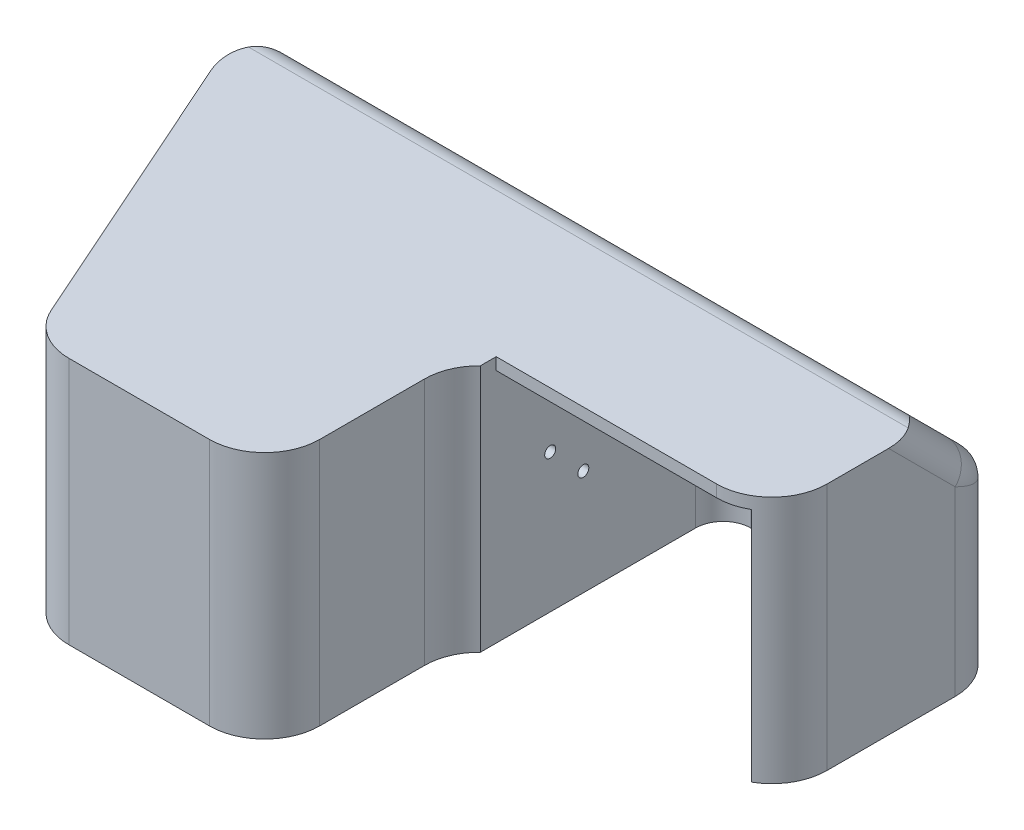
SolidWorks part; units mm, degrees
ref_plane "前视基准面" through (0, 0, 0) normal (0, 0, 1) x (1, 0, 0)
ref_plane "上视基准面" through (0, 0, 0) normal (0, 1, 0) x (1, 0, 0)
ref_plane "右视基准面" through (0, 0, 0) normal (1, 0, 0) x (0, 0, -1)
other "Configuration Table"
sketch "草图2" plane through (0, 0, 0) normal (0, 1, 0) x (1, 0, 0)
  line L0 (-10, 0) -> (-35.5013, 0)
  line L1 (53, 49) -> (53, 63)
  line L3 (0, 10) -> (0, 29)
  line L4 (10, 39) -> (43, 39)
  line L5 (-70, 63) -> (-44.6394, 5.9386)
  line L6 (-42, 0) -> (-75.4277, 75.2123)
  line L7 (-70.8587, 82.243) -> (43, 82.243)
  line L8 (53, 72.243) -> (53, 63)
  arc A0 (0, 29) -> (10, 39) centre (10, 29) cw
  arc A1 (53, 72.243) -> (43, 82.243) centre (43, 72.243) ccw
  arc A2 (53, 49) -> (43, 39) centre (43, 49) cw
  arc A3 (0, 10) -> (-10, 0) centre (-10, 10) cw
  arc A4 (-35.5013, 0) -> (-44.6394, 5.9386) centre (-35.5013, 10) cw
  arc A5 (-70.8587, 82.243) -> (-75.4277, 75.2123) centre (-70.8587, 77.243) ccw
  point P11 (0, 39)
  point P16 (53, 39)
  point P19 (0, 0)
  dimension "D3" = 10
  dimension "D6" = 5
  dimension "D1" = 42
  dimension "D2" = 123
  dimension "D4" = 39
  dimension "D5" = 53
extrude "凸台-拉伸3" add sketch "草图2" along normal blind 45 contours L7 A5 L6 L5 A4 L0 A3 L3 A0 L4 A2 L1 L8 A1 region at (-13.0814, 0, -50.1616)
sketch "草图3" plane through (53, 0, 0) normal (1, 0, 0) x (0, 0, -1)
  line L0 (82.243, 45) -> (67.243, 45)
  line L1 (49, 45) -> (72.243, 45) construction
  line L2 (82.243, 45) -> (82.243, 30)
  line L3 (67.243, 45) -> (82.243, 30)
  dimension "D1" = 15
  dimension "D2" = 15
extrude "切除-拉伸1" cut sketch "草图3" against normal blind 4005
fillet "圆角1" radius 5 6 edges at (-73.6568, 41.0153, -71.2277) (-75.0511, 32.2754, -79.9676) (53, 42.5, -69.743) (50.0711, 32.9289, -79.3141) (-13.9293, 30, -82.243) (-9.4429, 45, -67.243)
sketch "草图4" plane through (0, 0, 0) normal (0, -1, 0) x (1, 0, 0)
  line L1 (3, -39) -> (48, -39)
  line L2 (3, -39) -> (3, -74)
  line L3 (8, -79) -> (43, -79)
  line L4 (48, -39) -> (48, -74)
  line L5 (10, -39) -> (43, -39) construction
  line L6 (53, -49) -> (53, -72.243) construction
  arc A0 (48, -74) -> (43, -79) centre (43, -74) cw
  arc A1 (8, -79) -> (3, -74) centre (8, -74) cw
  point P10 (48, -79)
  dimension "D5" = 5
  dimension "D1" = 45
  dimension "D2" = 40
  dimension "D3" = 0
  dimension "D4" = 5
extrude "切除-拉伸3" cut sketch "草图4" against normal blind 25
sketch "草图5" plane through (0, 0, 0) normal (0, -1, 0) x (1, 0, 0)
  line L1 (3, -39) -> (48.6547, -39)
  line L2 (3, -39) -> (3, 1.5945)
  line L3 (3, 1.5945) -> (48.6547, 1.5945)
  line L4 (48.6547, -39) -> (48.6547, 1.5945)
extrude "切除-拉伸4" cut sketch "草图5" against normal blind 25 contours L2 L3 L4 L1
sketch "草图6" plane through (0, 0, -39) normal (0, 0, 1) x (1, 0, 0)
  line L0 (3, 25) -> (3, 0) construction
  line L1 (48, 25) -> (3, 25)
  line L2 (48, 25) -> (48, 42.8186)
  line L3 (48, 42.8186) -> (3, 42.8186)
  line L4 (3, 25) -> (3, 42.8186)
  dimension "D1" = 0
sketch "草图7" plane through (0, 56.1215, -56.1215) normal (0, 0.7071, -0.7071) x (-1, 0, 0)
  line L1 (70.8587, -34.8703) -> (-48, -34.8703)
  line L2 (70.8587, -34.8703) -> (70.8587, -17.7993)
  line L3 (70.8587, -17.7993) -> (-48, -17.7993)
  line L4 (-48, -34.8703) -> (-48, -17.7993)
extrude "切除-拉伸7" cut sketch "草图6" against normal offset from surface (41.172 mm away) 5 contours L2 L3 L4 L1 up to face at (0.7366, 37.0858, -75.1573)
sketch "草图8" plane through (0, 25, 0) normal (0, 1, 0) x (1, 0, 0)
  line L1 (8, 80.172) -> (43, 80.172)
  line L2 (3, 75.172) -> (3, 74)
  line L3 (3, 74) -> (48, 74)
  line L4 (48, 75.172) -> (48, 74)
  arc A0 (48, 75.172) -> (43, 80.172) centre (43, 75.172) ccw
  arc A1 (8, 80.172) -> (3, 75.172) centre (8, 75.172) ccw
  point P10 (3, 80.172)
  dimension "D1" = 5
extrude "切除-拉伸8" cut sketch "草图8" against normal blind 25
sketch "草图9" plane through (0, 25, 0) normal (0, -1, 0) x (-1, 0, 0)
  line L1 (-10, 39) -> (-3, 39)
  line L2 (-10, 39) -> (-10, 36.1414)
  line L3 (-10, 36.1414) -> (-3, 36.1414)
  line L4 (-3, 39) -> (-3, 36.1414)
extrude "切除-拉伸9" cut sketch "草图9" against normal blind 25
sketch "草图10" plane through (0, 0, 0) normal (0, -1, 0) x (-1, 0, 0)
  line L0 (5.1124, 80.7786) -> (65.8587, 80.7786)
  line L1 (70.8587, 80.7786) -> (-48, 80.7786) construction
  line L2 (70.8587, 75.7786) -> (70.8587, 74.743)
  line L3 (70.8587, 80.7786) -> (70.8587, 68.7075) construction
  line L4 (70.8587, 74.743) -> (70.8587, 69.7769)
  line L5 (70.4212, 67.7316) -> (43.1232, 6.836)
  line L6 (40.8629, 4.4428) -> (36.512, 2.1859)
  line L7 (34.2097, 1.6243) -> (9.6823, 1.6243)
  line L8 (7.637, 2.0618) -> (5.2194, 3.1455)
  line L9 (2.5922, 5.9281) -> (1.9136, 7.7095)
  line L10 (1.5873, 9.3783) -> (0.1136, 75.6674)
  arc A0 (70.4212, 67.7316) -> (70.8587, 69.7769) centre (65.8587, 69.7769) ccw
  arc A1 (65.8587, 80.7786) -> (70.8587, 75.7786) centre (65.8587, 75.7786) cw
  arc A2 (1.9136, 7.7095) -> (1.5873, 9.3783) centre (6.586, 9.4895) cw
  arc A3 (5.2194, 3.1455) -> (2.5922, 5.9281) centre (7.2647, 7.7081) cw
  arc A4 (9.6823, 1.6243) -> (7.637, 2.0618) centre (9.6823, 6.6243) cw
  arc A5 (36.512, 2.1859) -> (34.2097, 1.6243) centre (34.2097, 6.6243) cw
  arc A6 (43.1232, 6.836) -> (40.8629, 4.4428) centre (38.5606, 8.8812) cw
  arc A7 (0.1136, 75.6674) -> (5.1124, 80.7786) centre (5.1124, 75.7786) cw
  point P17 (70.8587, 68.7075)
  point P20 (70.8587, 80.7786)
  point P33 (0, 80.7786)
  dimension "D1" = 5
  dimension "D2" = 5
extrude "切除-拉伸10" cut sketch "草图10" against normal offset from surface (30 mm away) 15 up to face at (-1.3395, 45, -34.7687)
sketch "草图11" plane through (0, 30, 0) normal (0, -1, 0) x (1, 0, 0)
  line L0 (3, -62.3534) -> (-60.2895, -62.3534)
  line L1 (-43.1232, -6.836) -> (-70.4212, -67.7316) construction
  line L2 (-64.852, -55.3081) -> (-43.1232, -6.836)
  line L3 (-43.1232, -6.836) -> (-40.8629, -4.4428)
  line L4 (-40.8629, -4.4428) -> (-37.3488, -2.62)
  line L5 (-36.512, -2.1859) -> (-40.8629, -4.4428) construction
  line L6 (-37.3488, -2.62) -> (-34.2097, -1.6243)
  line L7 (-34.2097, -1.6243) -> (-8.6365, -1.7349)
  line L8 (-8.6365, -1.7349) -> (-3.629, -4.2755)
  line L9 (-3.629, -4.2755) -> (-1.5873, -9.3783)
  line L10 (-1.5873, -9.3783) -> (-0.4096, -62.3534)
  line L11 (-0.1136, -75.6674) -> (-1.5873, -9.3783) construction
  line L12 (-0.4096, -62.3534) -> (-68.0102, -62.3534)
  arc A0 (-40.8629, -4.4428) -> (-43.1232, -6.836) centre (-38.5606, -8.8812) ccw construction
  arc A1 (-40.8629, -4.4428) -> (-43.1232, -6.836) centre (-38.5606, -8.8812) ccw construction
  arc A2 (-7.637, -2.0618) -> (-9.6823, -1.6243) centre (-9.6823, -6.6243) ccw construction
  arc A3 (-2.5922, -5.9281) -> (-5.2194, -3.1455) centre (-7.2647, -7.7081) ccw construction
  arc A4 (-60.2895, -62.3534) -> (-64.852, -55.3081) centre (-60.2895, -57.3534) cw
  line M15 (-0.1136, -75.6674) -> (-1.5873, -9.3783)
  line M23 (-36.512, -2.1859) -> (-40.8629, -4.4428)
  line M25 (-43.1232, -6.836) -> (-70.4212, -67.7316)
  dimension "D1" = 5
extrude "切除-拉伸12" cut sketch "草图11" against normal offset from surface (13 mm away) 13 contours A4 L0 L9 L8 L7 L6 L3 M15 M23 M25 region at (-28.2559, 30, -34.88) up to face at (-29.156, 30, -31.0499)
sketch "草图12" plane through (0, 0, -62.3534) normal (0, 0, 1) x (1, 0, 0)
  line L1 (-60.2895, 43) -> (-0.4096, 43)
  line L2 (-60.2895, 43) -> (-60.2895, 30)
  line L3 (-60.2895, 30) -> (-0.4096, 30)
  line L4 (-0.4096, 43) -> (-0.4096, 30)
extrude "切除-拉伸13" cut sketch "草图12" against normal offset from surface (2.647 mm away) 3 up to face at (0.7366, 37.0858, -75.1573)
sketch "草图14" plane through (3, 0, 0) normal (1, 0, 0) x (0, 0, -1)
  circle A0 centre (54.8011, 25.1439) radius 6
  circle A1 centre (54.8011, 31.1439) radius 1
  circle A2 centre (48.8011, 25.1439) radius 1
  circle A3 centre (54.8011, 19.1439) radius 1
  circle A4 centre (60.8011, 25.1439) radius 1
  dimension "D1" = 12
extrude "切除-拉伸14" cut sketch "草图14" against normal blind 3 contours A2 | A1 | A3
sketch "草图15" plane through (0, 0, -82.243) normal (0, 0, -1) x (-1, 0, 0)
  line L1 (-31.0713, 25.2494) -> (58.9287, 25.2494)
  line L2 (-31.0713, 25.2494) -> (-31.0713, 5.2661)
  line L3 (-31.0713, 5.2661) -> (58.9287, 5.2661)
  line L4 (58.9287, 25.2494) -> (58.9287, 5.2661)
  line L5 (70.8587, 27.9289) -> (70.8587, 0) construction
  circle A0 centre (-31.0713, 15.2577) radius 6
  circle A1 centre (13.9287, 15.2577) radius 6
  circle A2 centre (58.9287, 15.2577) radius 6
  circle A3 centre (-31.0713, 21.2577) radius 1
  circle A4 centre (-37.0713, 15.2577) radius 1
  circle A5 centre (-25.0713, 15.2577) radius 1
  circle A6 centre (-31.0713, 9.2577) radius 1
  circle A7 centre (13.9287, 21.2577) radius 1
  circle A8 centre (7.9287, 15.2577) radius 1
  circle A9 centre (13.9287, 9.2577) radius 1
  circle A10 centre (19.9287, 15.2577) radius 1
  circle A11 centre (58.9287, 21.2577) radius 1
  circle A12 centre (52.9287, 15.2577) radius 1
  circle A13 centre (64.9287, 15.2577) radius 1
  circle A14 centre (58.9287, 9.2577) radius 1
  dimension "D3" = 12
  dimension "D4" = 12
  dimension "D1" = 90
  dimension "D2" = 11.93
  dimension "D5" = 45
extrude "切除-拉伸15" cut sketch "草图15" against normal blind 10 contours A4 | A3 | A5 | A6 | A7 | A8 | A10 | A9 | A11 | A12 | A14 | A13
